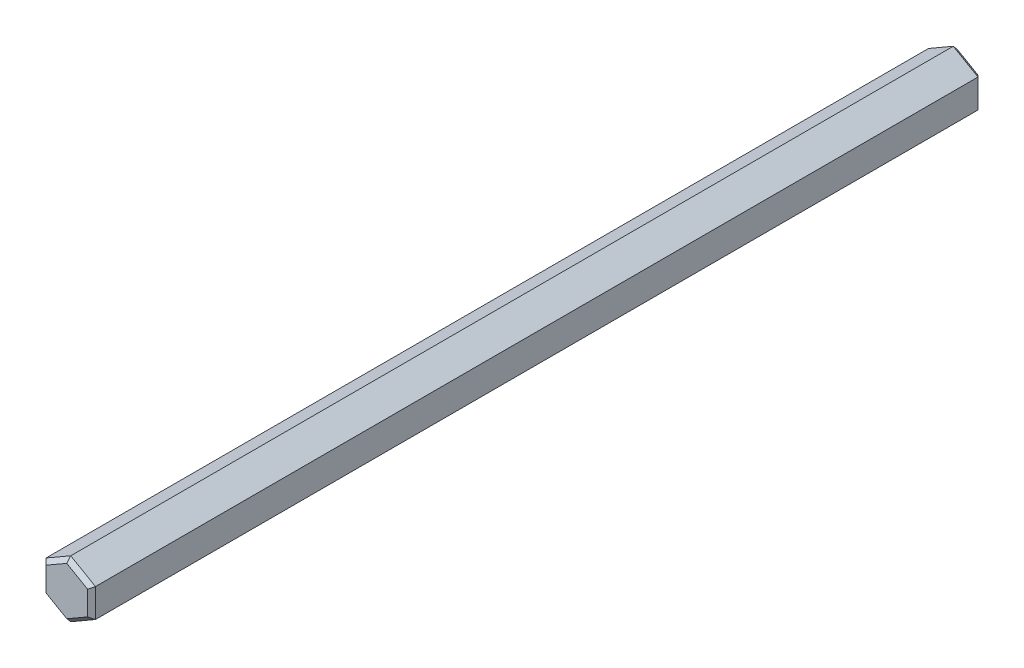
SolidWorks part; units mm, degrees
ref_plane "Front Plane" through (0, 0, 0) normal (0, 0, 1) x (1, 0, 0)
ref_plane "Top Plane" through (0, 0, 0) normal (0, 1, 0) x (1, 0, 0)
ref_plane "Right Plane" through (0, 0, 0) normal (1, 0, 0) x (0, 0, -1)
ref_plane "Plane1" through (0, 0, 75) normal (0, 0, 1) x (1, 0, 0)
sketch "Sketch1" plane through (0, 0, 75) normal (0, 0, 1) x (1, 0, 0)
  line L0 (0, -2.8868) -> (2.5, -1.4434)
  line L1 (2.5, -1.4434) -> (2.5, 1.4434)
  line L2 (2.5, 1.4434) -> (0, 2.8868)
  line L3 (0, 2.8868) -> (-2.5, 1.4434)
  line L4 (-2.5, 1.4434) -> (-2.5, -1.4434)
  line L5 (-2.5, -1.4434) -> (0, -2.8868)
extrude "Boss-Extrude1" add sketch "Sketch1" against normal blind 90
chamfer "Chamfer1" distance 0.4 angle 45 12 edges at (-2.5, 0, -15) (-1.25, -2.1651, -15) (-1.25, 2.1651, -15) (1.25, -2.1651, -15) (1.25, 2.1651, -15) (2.5, 0, -15) (-1.25, 2.1651, 75) (-2.5, 0, 75) (1.25, 2.1651, 75) (-1.25, -2.1651, 75) (2.5, 0, 75) (1.25, -2.1651, 75)
